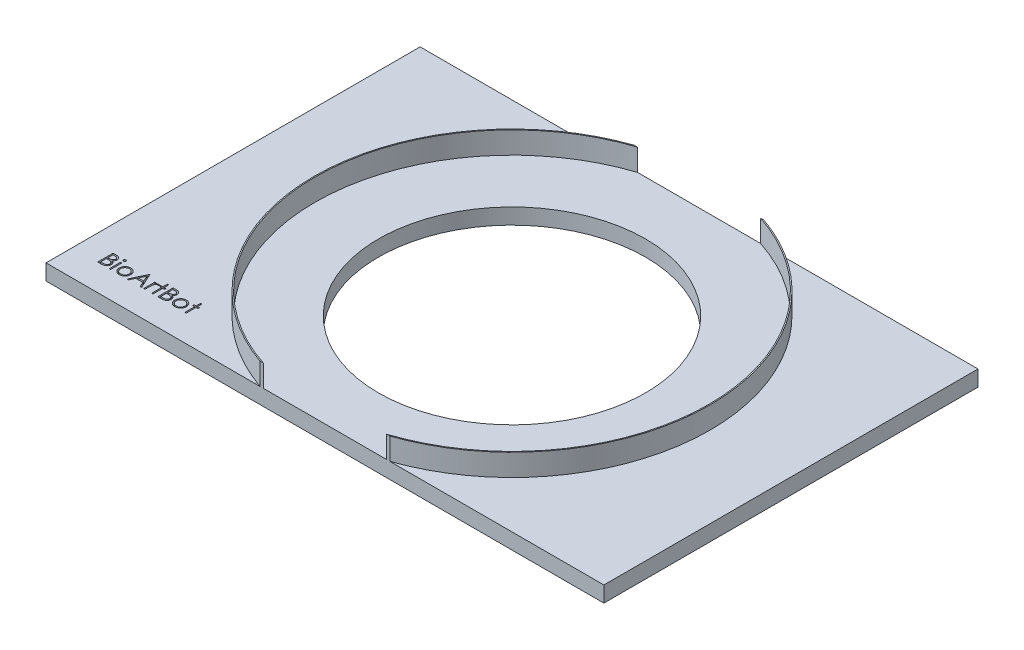
SolidWorks part; units mm, degrees
ref_plane "Front Plane" through (0, 0, 0) normal (0, 0, 1) x (1, 0, 0)
ref_plane "Top Plane" through (0, 0, 0) normal (0, 1, 0) x (1, 0, 0)
ref_plane "Right Plane" through (0, 0, 0) normal (1, 0, 0) x (0, 0, -1)
sketch "Sketch1" plane through (0, 0, 0) normal (0, 1, 0) x (1, 0, 0)
  line L1 (-63.75, -42.75) -> (63.75, -42.75)
  line L2 (-63.75, -42.75) -> (-63.75, 42.75)
  line L3 (-63.75, 42.75) -> (63.75, 42.75)
  line L4 (63.75, -42.75) -> (63.75, 42.75)
  line L5 (-63.75, -42.75) -> (63.75, 42.75) construction
  line L6 (-63.75, 42.75) -> (63.75, -42.75) construction
  circle A0 centre (0, 0) radius 45
  circle A1 centre (0, 0) radius 45.25
  circle A2 centre (0, 0) radius 30.5
  point P0 (0, 0)
  dimension "D1" = 90
  dimension "D2" = 90.5
  dimension "D3" = 61
  dimension "D5" = 127.5
  dimension "D6" = 85.5
extrude "Boss-Extrude4" add sketch "Sketch1" against normal blind 3.6 contours A1 L3 L2 L1 | A1 L1 L4 L3 region at (-49.1445, 0, 0) region at (49.1445, 0, 0)
extrude "Boss-Extrude5" add sketch "Sketch1<6>" along normal blind 5 separate body contours L3 A1 L1 A0 | L1 A1 L3 A0 region at (-45.159, 0, 0) region at (14.4418, 0, 42.659)
sketch "Sketch1<6>" plane through (0, 0, 0) normal (0, 1, 0) x (1, 0, 0) same geometry as "Sketch1"
extrude "Boss-Extrude7" add sketch "Sketch1<9>" against normal up to surface (3.6 mm away) contours L1 A0 L3 A2 | L3 A1 L1 A0 | L1 A1 L3 A0 up to face at (46.8956, -3.6, 0)
sketch "Sketch1<9>" plane through (0, 0, 0) normal (0, 1, 0) x (1, 0, 0) same geometry as "Sketch1"
sketch "Sketch2" plane through (0, 0, 0) normal (0, 1, 0) x (1, 0, 0)
  text T0 "BioArtBot"
extrude "Cut-Extrude1" cut sketch "Sketch2" against normal blind 1
